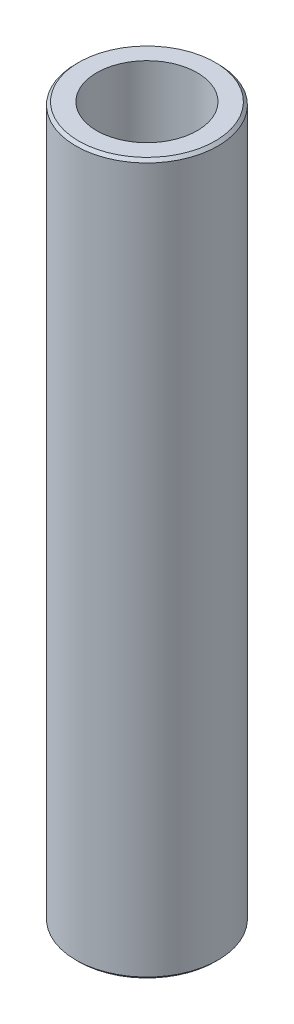
SolidWorks part; units mm, degrees
ref_plane "Front Plane" through (0, 0, 0) normal (0, 0, 1) x (1, 0, 0)
ref_plane "Top Plane" through (0, 0, 0) normal (0, 1, 0) x (1, 0, 0)
ref_plane "Right Plane" through (0, 0, 0) normal (1, 0, 0) x (0, 0, -1)
sketch "Sketch1" plane through (0, 0, 0) normal (0, 1, 0) x (1, 0, 0)
  circle A0 centre (0, 0) radius 60
  dimension "SHAFT_OD" = 120
extrude "Boss-Extrude1" add sketch "Sketch1" along normal blind 600
sketch "Sketch2" plane through (0, 0, 0) normal (0, 1, 0) x (1, 0, 0)
  circle A0 centre (0, 0) radius 42.4387
  dimension "BORE_D" = 84.8774
extrude "Cut-Extrude1" cut sketch "Sketch2" along normal through all
chamfer "Chamfer1" distance 2.4126 angle 45 2 edges at (0, 600, 60) (0, 0, 60)
